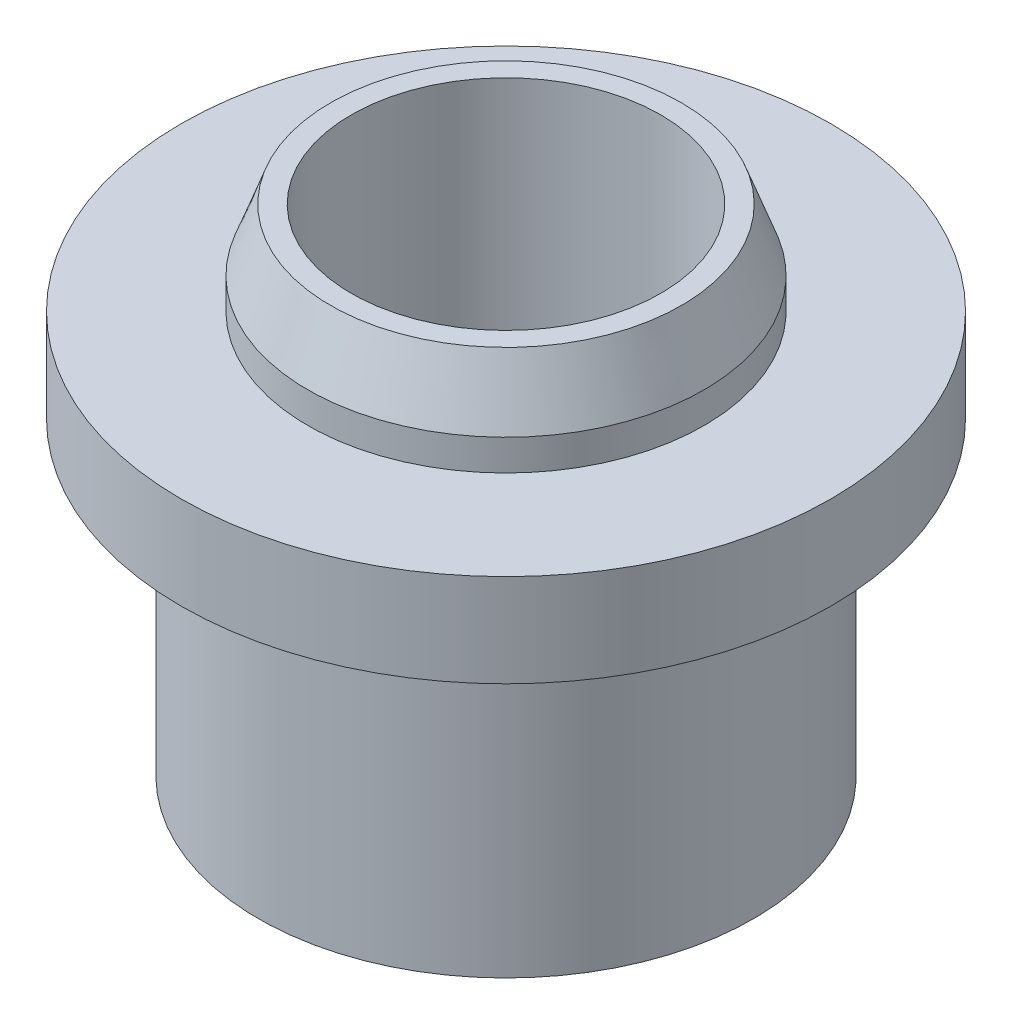
SolidWorks part; units mm, degrees
ref_plane "Front Plane" through (0, 0, 0) normal (0, 0, 1) x (1, 0, 0)
ref_plane "Top Plane" through (0, 0, 0) normal (0, 1, 0) x (1, 0, 0)
ref_plane "Right Plane" through (0, 0, 0) normal (1, 0, 0) x (0, 0, -1)
sketch "Sketch1" plane through (0, 0, 0) normal (0, 0, 1) x (1, 0, 0)
  line L0 (0, 0) -> (0, 5.4195) construction
  line L1 (2.5, -0.0763) -> (2.5, 6.4237)
  line L2 (3.2, 6.4237) -> (5.25, 6.4237)
  line L3 (5.25, 6.4237) -> (5.25, 4.9237)
  line L4 (5.25, 4.9237) -> (4, 4.9237)
  line L5 (4, 4.9237) -> (4, -0.0763)
  line L6 (4, -0.0763) -> (2.5, -0.0763)
  line L7 (2.5, 6.4237) -> (2.5, 7.9237)
  line L8 (2.5, 7.9237) -> (2.836, 7.9237)
  line L10 (2.836, 7.9237) -> (3.2, 6.9237)
  line L11 (3.2, 6.9237) -> (3.2, 6.4237)
  dimension "D1" = 8
  dimension "D2" = 5
  dimension "D3" = 1.5
  dimension "D4" = 5
  dimension "D5" = 10.5
  dimension "D6" = 3.2
  dimension "D7" = 1.5
  dimension "D8" = 110
  dimension "D9" = 0.5
revolve "Revolve1" add sketch "Sketch1" angle 360 about L0
